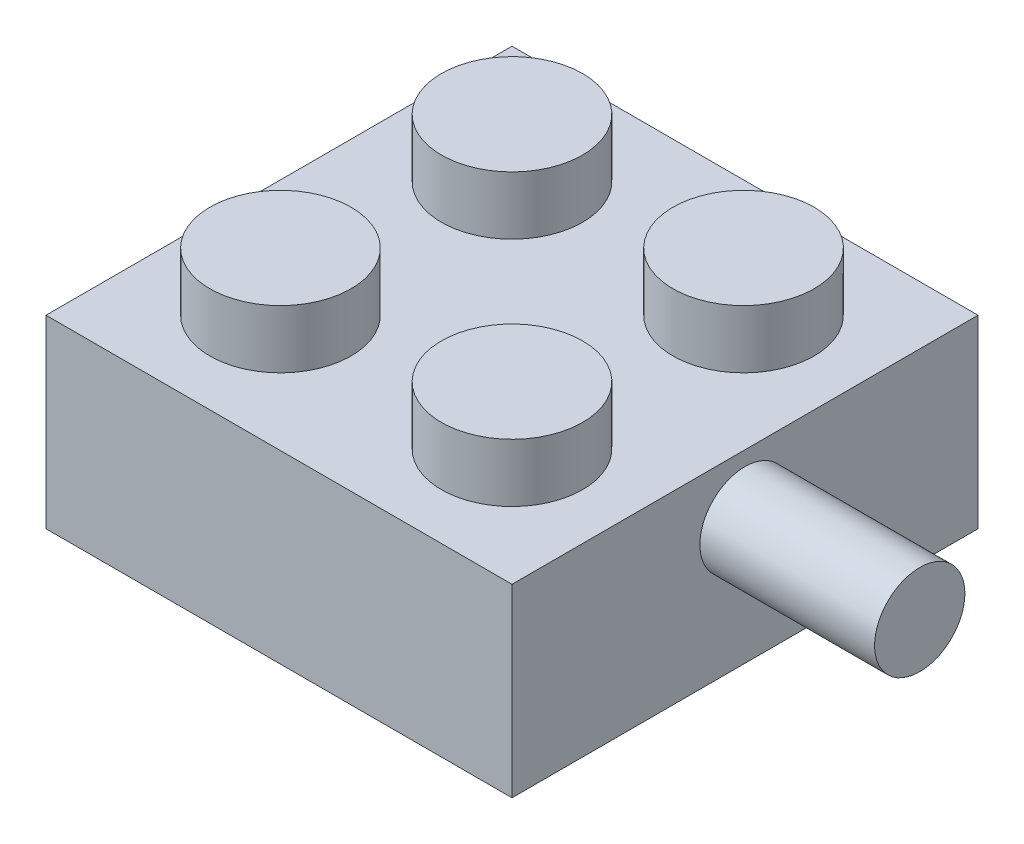
SolidWorks part; units mm, degrees
ref_plane "Front Plane" through (0, 0, 0) normal (0, 0, 1) x (1, 0, 0)
ref_plane "Top Plane" through (0, 0, 0) normal (0, 1, 0) x (1, 0, 0)
ref_plane "Right Plane" through (0, 0, 0) normal (1, 0, 0) x (0, 0, -1)
sketch "Sketch1" plane through (0, 0, 0) normal (0, 1, 0) x (1, 0, 0)
  line L0 (0, 0) -> (0, 50000) construction
  line L1 (-8, -8) -> (8, -8)
  line L2 (-8, -8) -> (-8, 8)
  line L3 (-8, 8) -> (8, 8)
  line L4 (8, -8) -> (8, 8)
  line L5 (-8, -8) -> (8, 8) construction
  line L6 (-8, 8) -> (8, -8) construction
  line L7 (0, 0) -> (50000, 0) construction
  circle A0 centre (3.975, 3.975) radius 2.425
  circle A1 centre (3.975, -3.975) radius 2.425
  circle A2 centre (-3.975, -3.975) radius 2.425
  circle A3 centre (-3.975, 3.975) radius 2.425
  point P0 (0, 0)
  point P18 (-6.4, 3.975)
  point P19 (6.4, 3.975)
  point P20 (-3.975, 6.4)
  point P21 (-3.975, -6.4)
  dimension "D2" = 4.85
  dimension "D1" = 16
  dimension "D3" = 12.8
  dimension "D4" = 12.8
extrude "Boss-Extrude1" add sketch "Sketch1" along normal blind 6.35 contours L1 L4 L3 L2
extrude "Boss-Extrude2" add sketch "Sketch1<3>" along normal blind 2 from surface contours A2 | A1 | A0 | A3 region at (3.975, 0, -3.975) region at (3.975, 0, 3.975) region at (-3.975, 0, 3.975) region at (-3.975, 0, -3.975) starting at face at (0, 6.35, 0)
sketch "Sketch1<3>" plane through (0, 0, 0) normal (0, 1, 0) x (1, 0, 0) same geometry as "Sketch1"
sketch "Sketch2" plane through (8, 0, 0) normal (1, 0, 0) x (0, 0, -1)
  line L0 (-8, 6.35) -> (8, 6.35) construction
  circle A0 centre (0, 4.3) radius 1.55
  circle A1 centre (0, 4.3) radius 2.05 construction
  dimension "D1" = 3.1
  dimension "D2" = 4.1
extrude "Boss-Extrude3" add sketch "Sketch2" along normal blind 6
